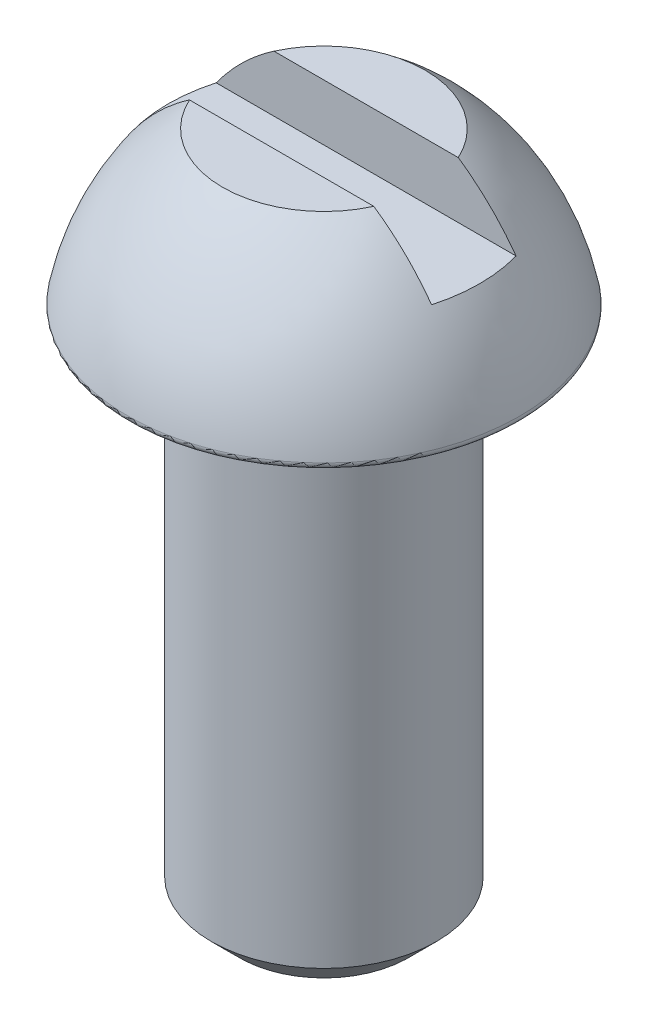
SolidWorks part; units mm, degrees
ref_plane "Спереди" through (0, 0, 0) normal (0, 0, 1) x (1, 0, 0)
ref_plane "Сверху" through (0, 0, 0) normal (0, 1, 0) x (1, 0, 0)
ref_plane "Справа" through (0, 0, 0) normal (1, 0, 0) x (0, 0, -1)
sketch "Эскиз1" plane through (0, 0, 0) normal (0, 0, 1) x (1, 0, 0)
  line L0 (3.5, 9.2) -> (2, 9.2)
  line L1 (0, 0) -> (0, 12)
  line L2 (2, 9.2) -> (2, 0.5)
  line L3 (2, 0.5) -> (1.5, 0)
  line L4 (1.5, 0) -> (0, 0)
  line L5 (0, 12) -> (1.8, 12)
  arc A0 (1.8, 12) -> (3.5, 9.2) centre (-0.8408, 8.4806) cw
  point P9 (0, 0)
  dimension "D2" = 1.8
  dimension "D3" = 4.4
  dimension "D1" = 12
  dimension "D4" = 1.5
  dimension "D5" = 2.8
  dimension "D6" = 3.5
  dimension "D7" = 45
  dimension "D9" = 2
revolve "Повернуть1" add sketch "Эскиз1" angle 360 about L1
fillet "Скругление1" radius 0.1 1 edges at (0, 9.2, -3.5)
sketch "Эскиз3" plane through (0, 12, 0) normal (0, 1, 0) x (-1, 0, 0)
  line L1 (4, -0.75) -> (-4, -0.75)
  line L2 (4, -0.75) -> (4, 0.75)
  line L3 (4, 0.75) -> (-4, 0.75)
  line L4 (-4, -0.75) -> (-4, 0.75)
  dimension "D1" = 1.5
  dimension "D2" = 0.75
  dimension "D3" = 8
  dimension "D4" = 4
extrude "Вырез-Вытянуть2" cut sketch "Эскиз3" against normal blind 1
ref_axis "Ось1" through (0, -104.1565, 0) along (0, 1, 0)
